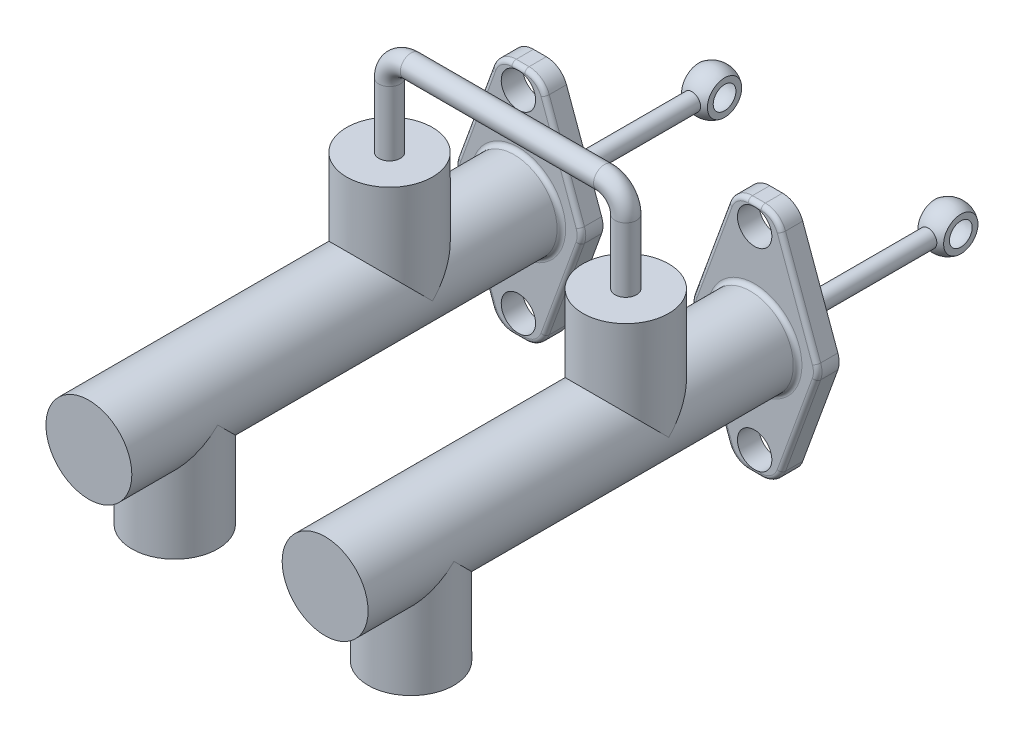
SolidWorks part; units mm, degrees
ref_plane "Płaszczyzna przednia" through (0, 0, 0) normal (0, 0, 1) x (1, 0, 0)
ref_plane "Płaszczyzna górna" through (0, 0, 0) normal (0, 1, 0) x (1, 0, 0)
ref_plane "Płaszczyzna prawa" through (0, 0, 0) normal (1, 0, 0) x (0, 0, -1)
sketch "Szkic1" plane through (0, 0, 0) normal (0, 0, 1) x (1, 0, 0)
  line L0 (0, 0) -> (0, 14.8807) construction
  circle A0 centre (-27.5, 0) radius 10
  circle A1 centre (27.5, 0) radius 10
  dimension "D1" = 20
  dimension "D2" = 55
extrude "Dodanie-wyciągnięcie1" add sketch "Szkic1" along normal mid plane 100
sketch "Szkic2" plane through (0, 0, -50) normal (0, 0, -1) x (-1, 0, 0)
  line L0 (-22.5, 27.5) -> (-32.5, 27.5)
  line L1 (-32.5, 27.5) -> (-42.5, 0)
  line L2 (-42.5, 0) -> (-32.5, -27.5)
  line L3 (-32.5, -27.5) -> (-22.5, -27.5)
  line L4 (-22.5, -27.5) -> (-12.5, 0)
  line L5 (-12.5, 0) -> (-22.5, 27.5)
  line L6 (-27.5, 0) -> (-27.5, 40.9003) construction
  line L7 (-27.5, 0) -> (-56.3461, 0) construction
  line L8 (0, 0) -> (0, 40.9003) construction
  line L9 (27.5, 0) -> (56.3461, 0) construction
  line L10 (27.5, 0) -> (27.5, 40.9003) construction
  line L11 (12.5, 0) -> (22.5, 27.5)
  line L12 (22.5, -27.5) -> (12.5, 0)
  line L13 (32.5, -27.5) -> (22.5, -27.5)
  line L14 (42.5, 0) -> (32.5, -27.5)
  line L15 (32.5, 27.5) -> (42.5, 0)
  line L16 (22.5, 27.5) -> (32.5, 27.5)
  circle A0 centre (-27.5, 22.5) radius 4
  circle A1 centre (-27.5, -22.5) radius 4
  circle A2 centre (27.5, -22.5) radius 4
  circle A3 centre (27.5, 22.5) radius 4
  dimension "D4" = 45
  dimension "D5" = 8
  dimension "D1" = 10
  dimension "D2" = 30
  dimension "D3" = 55
extrude "Dodanie-wyciągnięcie2" add sketch "Szkic2" along normal blind 5
fillet "Zaokrąglenie1" radius 5 6 edges at (-22.5, 27.5, -52.5) (-12.5, 0, -52.5) (-22.5, -27.5, -52.5) (-32.5, -27.5, -52.5) (-42.5, 0, -52.5) (-32.5, 27.5, -52.5)
fillet "Zaokrąglenie2" radius 5 6 edges at (12.5, 0, -52.5) (22.5, -27.5, -52.5) (32.5, -27.5, -52.5) (42.5, 0, -52.5) (32.5, 27.5, -52.5) (22.5, 27.5, -52.5)
fillet "Zaokrąglenie3" radius 1 13 edges at (-12.8203, 0, -50) (-17.2123, 12.9587, -50) (-23.1337, 26.5953, -50) (-31.8663, 26.5953, -50) (-37.7877, 12.9587, -50) (-42.1797, 0, -50) (-37.7877, -12.9587, -50) (-31.8663, -26.5953, -50) (-23.1337, -26.5953, -50) (-17.2123, -12.9587, -50) (-17.5, 0, -50) (-27.5, 27.5, -50) (-27.5, -27.5, -50)
fillet "Zaokrąglenie4" radius 1 13 edges at (42.1797, 0, -50) (37.7877, 12.9587, -50) (31.8663, 26.5953, -50) (27.5, 27.5, -50) (23.1337, 26.5953, -50) (17.2123, 12.9587, -50) (12.8203, 0, -50) (17.2123, -12.9587, -50) (23.1337, -26.5953, -50) (27.5, -27.5, -50) (31.8663, -26.5953, -50) (37.7877, -12.9587, -50) (37.5, 0, -50)
sketch "Szkic3" plane through (0, 0, 0) normal (0, 1, 0) x (1, 0, 0)
  line L0 (27.5, -50) -> (27.5, 106.4766) construction
  line L6 (17.5, -50) -> (37.5, -50) construction
  line L7 (31.5, 55) -> (23.5, 55) construction
  line L8 (27.5, 55) -> (29.5, 55)
  line L9 (27.5, 55) -> (27.5, 91)
  line L11 (29.5, 55) -> (29.5, 90.4174)
  line L14 (27.5, 99) -> (27.5, 100)
  arc A0 (27.5, 91) -> (27.5, 99) centre (27.5, 95) ccw
  arc A1 (29.5, 90.4174) -> (27.5, 100) centre (27.5, 95) ccw
  dimension "D3" = 8
  dimension "D4" = 10
  dimension "D1" = 2
  dimension "D2" = 40
revolve "Obrót1" add sketch "Szkic3" angle 360 about L0
sketch "Szkic4" plane through (0, 0, 0) normal (0, 1, 0) x (1, 0, 0)
  line L0 (-27.5, -50) -> (-27.5, 310.5537) construction
  line L1 (-37.5, -50) -> (-17.5, -50) construction
  line L2 (-28.9979, 55) -> (-26.0021, 55) construction
  line L3 (-27.5, 55) -> (-29.5, 55)
  line L4 (-27.5, 55) -> (-27.5, 91)
  line L6 (-29.5, 55) -> (-29.5, 90.4174)
  line L7 (-27.5, 99) -> (-27.5, 100)
  arc A0 (-27.5, 99) -> (-27.5, 91) centre (-27.5, 95) ccw
  arc A1 (-27.5, 100) -> (-29.5, 90.4174) centre (-27.5, 95) ccw
  dimension "D3" = 8
  dimension "D4" = 10
  dimension "D1" = 40
  dimension "D2" = 2
revolve "Obrót2" add sketch "Szkic4" angle 360 about L0
sketch "Szkic5" plane through (0, 0, -55) normal (0, 0, -1) x (-1, 0, 0)
  line L1 (-30.5, -10) -> (-24.5, -10)
  line L2 (-30.5, -10) -> (-30.5, 10)
  line L3 (-30.5, 10) -> (-24.5, 10)
  line L4 (-24.5, -10) -> (-24.5, 10)
  line L5 (-30.5, -10) -> (-24.5, 10) construction
  line L6 (-30.5, 10) -> (-24.5, -10) construction
  line L11 (-33.5, -12.5) -> (-21.5, -12.5)
  line L12 (-33.5, -12.5) -> (-33.5, 12.5)
  line L13 (-33.5, 12.5) -> (-21.5, 12.5)
  line L14 (-21.5, -12.5) -> (-21.5, 12.5)
  line L15 (-33.5, -12.5) -> (-21.5, 12.5) construction
  line L16 (-33.5, 12.5) -> (-21.5, -12.5) construction
  line L17 (24.5, -10) -> (30.5, -10)
  line L18 (24.5, -10) -> (24.5, 10)
  line L19 (24.5, 10) -> (30.5, 10)
  line L20 (30.5, -10) -> (30.5, 10)
  line L21 (24.5, -10) -> (30.5, 10) construction
  line L22 (24.5, 10) -> (30.5, -10) construction
  line L23 (21.5, -12.5) -> (33.5, -12.5)
  line L24 (21.5, -12.5) -> (21.5, 12.5)
  line L25 (21.5, 12.5) -> (33.5, 12.5)
  line L26 (33.5, -12.5) -> (33.5, 12.5)
  line L27 (21.5, -12.5) -> (33.5, 12.5) construction
  line L28 (21.5, 12.5) -> (33.5, -12.5) construction
  point P0 (-27.5, 0)
  point P5 (-27.5, 0)
  point P6 (-27.5, 0)
  point P12 (27.5, 0)
  point P17 (27.5, 0)
  dimension "D1" = 6
  dimension "D2" = 20
  dimension "D3" = 12
  dimension "D4" = 25
  dimension "D5" = 6
  dimension "D6" = 20
  dimension "D7" = 12
  dimension "D8" = 25
extrude "Wytnij-wyciągnięcie1" cut sketch "Szkic5" along normal blind 50
sketch "Szkic6" plane through (0, 0, 0) normal (0, 1, 0) x (1, 0, 0)
  line L0 (-37.5, 49) -> (-37.5, -50) construction
  line L1 (-17.5, -50) -> (-17.5, 49) construction
  line L2 (0, 0) -> (0, 36.7421) construction
  line L3 (-38.5, 50) -> (-16.5, 50) construction
  circle A0 centre (-27.5, 20) radius 10
  circle A1 centre (27.5, 20) radius 10
  dimension "D1" = 30
extrude "Dodanie-wyciągnięcie3" add sketch "Szkic6" along normal blind 25
ref_plane "Płaszczyzna1" through (0, 0, -20) normal (0, 0, 1) x (1, 0, 0)
sketch "Szkic7" plane through (0, 0, -20) normal (0, 0, 1) x (1, 0, 0)
  line L0 (-27.5, 25) -> (-27.5, 40)
  line L1 (-22.5, 45) -> (22.5, 45)
  line L2 (27.5, 40) -> (27.5, 25)
  line L3 (-17.5, 25) -> (-37.5, 25) construction
  line L4 (37.5, 25) -> (17.5, 25) construction
  arc A0 (22.5, 45) -> (27.5, 40) centre (22.5, 40) cw
  arc A1 (-22.5, 45) -> (-27.5, 40) centre (-22.5, 40) ccw
  point P14 (-27.5, 45)
  dimension "D2" = 5
  dimension "D1" = 20
sweep "Wyciągnięcie po ścieżce1" add path "Szkic7" circular profile diameter 5 parameters "D3"=5
sketch "Szkic19" plane through (0, 0, 0) normal (0, 1, 0) x (1, 0, 0)
  line L0 (17.5, 20) -> (17.5, -50) construction
  line L1 (37.5, -50) -> (37.5, 20) construction
  line L2 (-37.5, 20) -> (-37.5, -50) construction
  line L3 (-17.5, -50) -> (-17.5, 20) construction
  line L4 (-37.5, -50) -> (-17.5, -50) construction
  circle A0 centre (27.5, -30) radius 10
  circle A1 centre (-27.5, -30) radius 10
  circle A2 centre (-27.5, -30) radius 6
  circle A3 centre (27.5, -30) radius 6
  dimension "D1" = 20
  dimension "D2" = 12
extrude "Dodanie-wyciągnięcie4" add sketch "Szkic19" against normal blind 25
